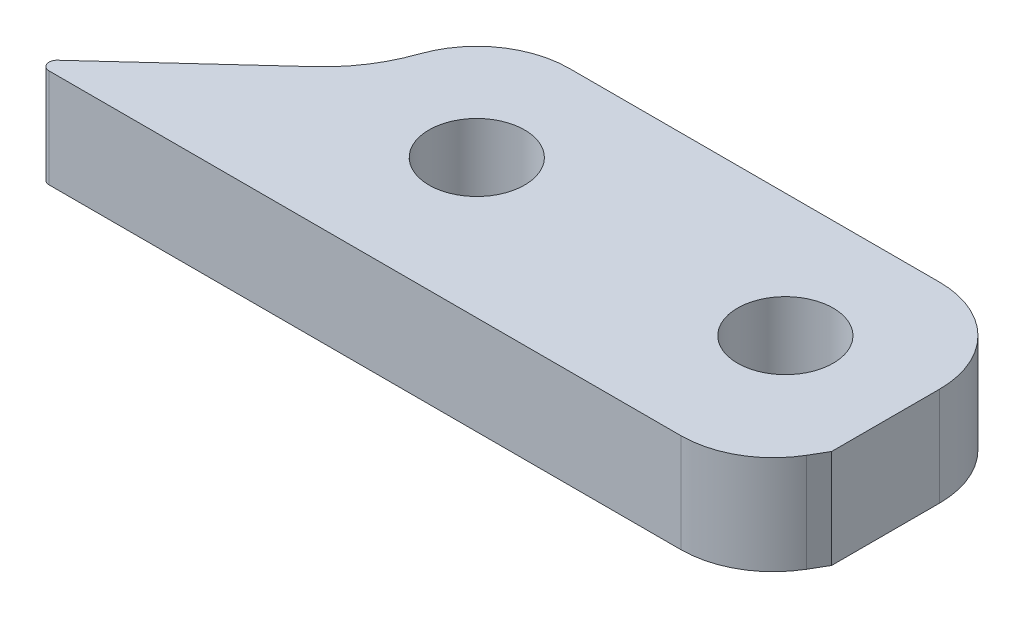
SolidWorks part; units mm, degrees
material "Titanium Ti-8Mn, Annealed"
ref_plane "Front Plane" through (0, 0, 0) normal (0, 0, 1) x (1, 0, 0)
ref_plane "Top Plane" through (0, 0, 0) normal (0, 1, 0) x (1, 0, 0)
ref_plane "Right Plane" through (0, 0, 0) normal (1, 0, 0) x (0, 0, -1)
sketch "Sketch1" plane through (0, 0, 0) normal (0, 1, 0) x (1, 0, 0)
  line L5 (36, -13) -> (36, 0)
  line L6 (36, 0) -> (0, 0)
  line L8 (36, -13) -> (33.6676, -17)
  line L9 (33.6676, -17) -> (-0.4555, -17)
  line L10 (0, 0) -> (0, -6)
  line L11 (0, -6) -> (-12, -17)
  line L12 (-12, -17) -> (-0.4555, -17)
  circle A0 centre (28, -8) radius 3.1
  circle A1 centre (8, -8) radius 3.1
  dimension "D8" = 6.2
  dimension "D9" = 6.2
  dimension "D1" = 13
  dimension "D2" = 36
  dimension "D3" = 8
  dimension "D4" = 12
  dimension "D5" = 6
  dimension "D10" = 20
  dimension "D11" = 8
extrude "Boss-Extrude1" add sketch "Sketch1" along normal blind 6.4
fillet "Fillet1" radius 6 3 edges at (33.6676, 3.2, 17) (36, 3.2, 0) (0, 3.2, 0)
fillet "Fillet2" radius 10 1 edges at (0, 3.2, 6)
fillet "Fillet3" radius 0.5 1 edges at (-12, 3.2, 17)
